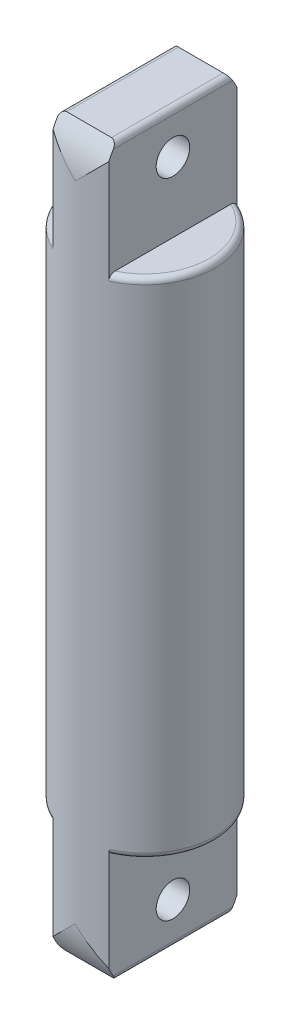
SolidWorks part; units mm, degrees
ref_plane "Front Plane" through (0, 0, 0) normal (0, 0, 1) x (1, 0, 0)
ref_plane "Top Plane" through (0, 0, 0) normal (0, 1, 0) x (1, 0, 0)
ref_plane "Right Plane" through (0, 0, 0) normal (1, 0, 0) x (0, 0, -1)
sketch "Sketch1" plane through (0, 0, 0) normal (0, 1, 0) x (1, 0, 0)
  circle A0 centre (0, 0) radius 125
  dimension "D1" = 250
extrude "Boss-Extrude1" add sketch "Sketch1" along normal blind 650
sketch "Sketch2" plane through (0, 650, 0) normal (0, 1, 0) x (1, 0, 0)
  line L1 (-50, 125) -> (50, 125)
  line L2 (-50, 125) -> (-50, -125)
  line L3 (-50, -125) -> (50, -125)
  line L4 (50, 125) -> (50, -125)
  line L5 (-50, 125) -> (50, -125) construction
  line L6 (-50, -125) -> (50, 125) construction
  circle A0 centre (0, 0) radius 125 construction
  circle A1 centre (0, 0) radius 125
  point P0 (0, 0)
  circle M1 centre (0, 0) radius 125
  dimension "D1" = 100
extrude "Cut-Extrude1" cut sketch "Sketch2" against normal blind 200 contours L2 M1 | L4 M1 region at (-80.9363, 650, 0) region at (80.9363, 650, 0)
sketch "Sketch3" plane through (-50, 0, 0) normal (-1, 0, 0) x (0, 0, 1)
  line L0 (114.5644, 450) -> (-114.5644, 450) construction
  line L1 (-114.5644, 650) -> (114.5644, 650) construction
  line L2 (-125, 450) -> (-125, 650)
  line L3 (-125, 650) -> (125, 650)
  line L4 (125, 650) -> (125, 450)
  circle A0 centre (0, 450) radius 125
  circle A1 centre (0, 575) radius 30
  dimension "D1" = 60
  dimension "D2" = 75
sketch "Sketch4" plane through (50, 0, 0) normal (1, 0, 0) x (0, 0, -1)
  line L0 (114.5644, 650) -> (-114.5644, 650) construction
  line L2 (125, 450) -> (125, 650)
  line L3 (125, 650) -> (-125, 650)
  line L4 (-125, 650) -> (-125, 450)
  line L5 (125, 575) -> (125, 650)
  line L6 (-125, 650) -> (125, 650)
  line L7 (-125, 650) -> (-125, 575)
  circle A0 centre (0, 575) radius 30
  circle A1 centre (0, 575) radius 125
  point P2 (0, 650)
  line M1 (114.5644, 650) -> (-114.5644, 650)
  line M2 (-114.5644, 650) -> (-114.5644, 450)
  line M4 (114.5644, 450) -> (114.5644, 650)
  dimension "D2" = 60
  dimension "D1" = 75
extrude "Cut-Extrude4" cut sketch "Sketch4" against normal through all contours A1 L2 L3 M4 | A1 M4 M1 | A1 M1 M2 | A1 L3 L4 M2 | A0 region at (50, 627.6469, -120.6177) region at (50, 642.0575, -109.9185) region at (50, 642.0575, 109.9185) region at (50, 627.6469, 120.6177) region at (50, 575, 0)
fillet "Fillet2" radius 10 2 edges at (50, 650, 0) (-50, 650, 0)
ref_plane "Plane1" through (0, 0, 0) normal (0, -1, 0) x (-1, 0, 0)
mirror "Mirror4" about plane through (0, 0, 0) normal (0, -1, 0) of "Fillet2", "Cut-Extrude4", "Cut-Extrude1", "Boss-Extrude1"
fillet "Fillet3" radius 10 2 edges at (125, 450, 0) (-125, 450, 0)
fillet "Fillet4" radius 10 2 edges at (-125, -450, 0) (125, -450, 0)
